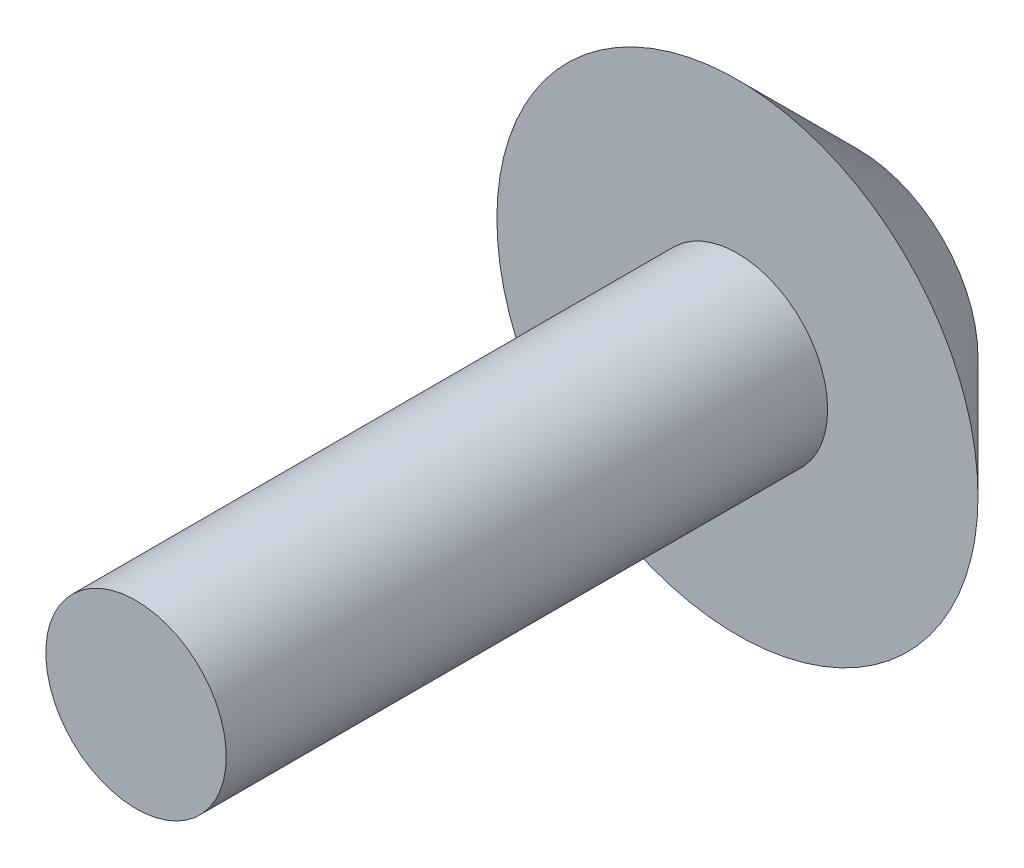
SolidWorks part; units mm, degrees
ref_plane "Front Plane" through (0, 0, 0) normal (0, 0, 1) x (1, 0, 0)
ref_plane "Top Plane" through (0, 0, 0) normal (0, 1, 0) x (1, 0, 0)
ref_plane "Right Plane" through (0, 0, 0) normal (1, 0, 0) x (0, 0, -1)
sketch "Sketch1" plane through (0, 0, 0) normal (0, 0, 1) x (1, 0, 0)
  circle A0 centre (0, 0) radius 4
  circle A1 centre (0, 0) radius 1.5
  dimension "D1" = 8
  dimension "D2" = 3
extrude "Boss-Extrude2" add sketch "Sketch1" along normal blind 10 contours A1
extrude "Boss-Extrude4" add sketch "Sketch1<8>" against normal blind 2 separate body
sketch "Sketch1<8>" plane through (0, 0, 0) normal (0, 0, 1) x (1, 0, 0) same geometry as "Sketch1"
sketch "Sketch2" plane through (0, 0, 0) normal (0, 0, -1) x (-1, 0, 0)
  circle A0 centre (0, 0) radius 1.5
extrude "Boss-Extrude5" add sketch "Sketch2" along normal blind 2
sketch "Sketch3" plane through (0, 0, -2) normal (0, 0, -1) x (-1, 0, 0)
  line L1 (0, 1.947) -> (-1.6862, 0.9735)
  line L2 (-1.6862, 0.9735) -> (-1.6862, -0.9735)
  line L3 (-1.6862, -0.9735) -> (0, -1.947)
  line L4 (0, -1.947) -> (1.6862, -0.9735)
  line L5 (1.6862, -0.9735) -> (1.6862, 0.9735)
  line L6 (1.6862, 0.9735) -> (0, 1.947)
  circle A0 centre (0, 0) radius 1.6862 construction
extrude "Cut-Extrude2" cut sketch "Sketch3" against normal blind 1.5
chamfer "Chamfer1" distance 2 angle 45 1 edges at (4, 0, -2)
